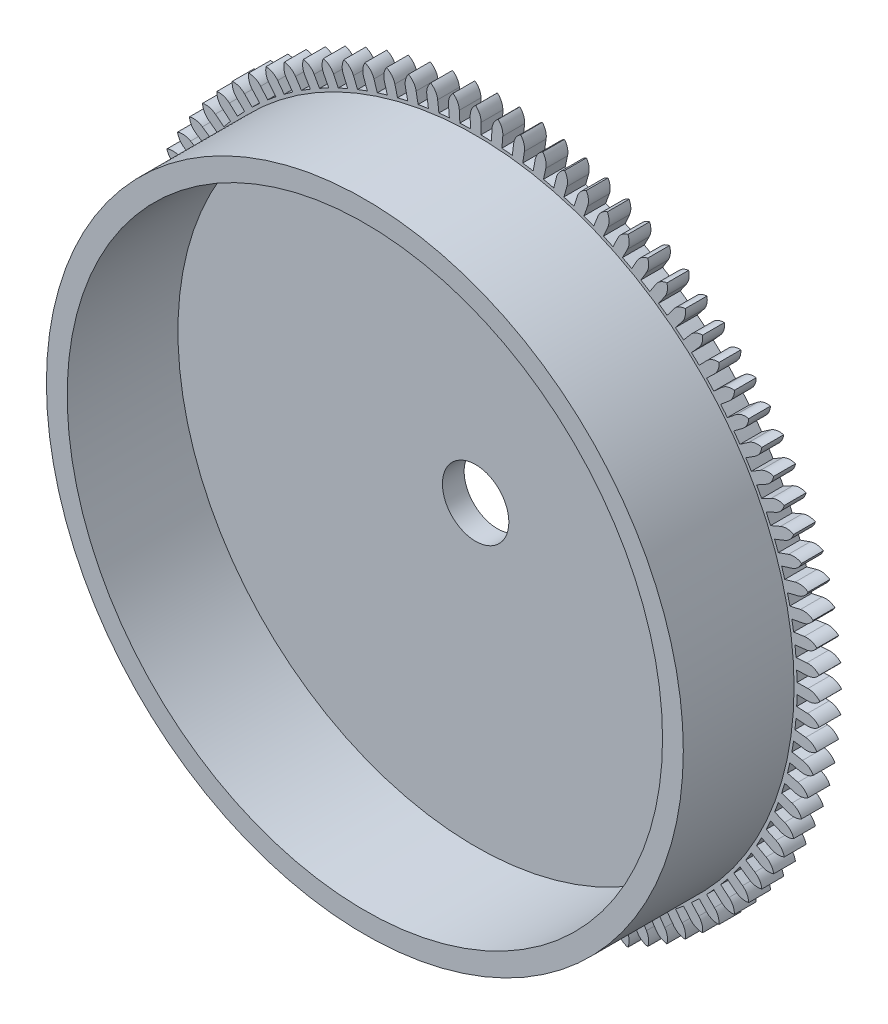
SolidWorks part; units mm, degrees
material "AISI 321 Annealed Stainless Steel (SS)"
ref_plane "Front Plane" through (0, 0, 0) normal (0, 0, 1) x (1, 0, 0)
ref_plane "Top Plane" through (0, 0, 0) normal (0, 1, 0) x (1, 0, 0)
ref_plane "Right Plane" through (0, 0, 0) normal (1, 0, 0) x (0, 0, -1)
sketch "Sketch1" plane through (0, 0, 0) normal (0, 0, 1) x (1, 0, 0)
  line L0 (0, 0) -> (0, 13.0514) construction
  line L1 (-0.1899, 11.6057) -> (-0.1963, 11.9984)
  line L2 (0.1899, 11.6057) -> (0.1963, 11.9984)
  line L3 (0.5695, 11.5933) -> (0.5888, 11.9855)
  line L4 (0.9486, 11.5685) -> (0.9807, 11.9599)
  line L5 (1.3266, 11.5312) -> (1.3714, 11.9214)
  line L6 (1.7031, 11.4817) -> (1.7608, 11.8701)
  line L7 (2.0779, 11.4198) -> (2.1482, 11.8062)
  line L8 (2.4504, 11.3457) -> (2.5333, 11.7295)
  line L9 (2.8203, 11.2594) -> (2.9158, 11.6404)
  line L10 (3.1872, 11.1611) -> (3.2951, 11.5387)
  line L11 (3.5507, 11.0509) -> (3.6708, 11.4248)
  line L12 (3.9104, 10.9288) -> (4.0427, 11.2985)
  line L13 (4.2659, 10.795) -> (4.4102, 11.1602)
  line L14 (4.6168, 10.6496) -> (4.773, 11.0099)
  line L15 (4.9628, 10.4929) -> (5.1307, 10.8479)
  line L16 (5.3034, 10.3249) -> (5.4828, 10.6742)
  line L17 (5.6384, 10.1458) -> (5.8292, 10.4891)
  line L18 (5.9673, 9.9559) -> (6.1692, 10.2927)
  line L19 (6.2899, 9.7553) -> (6.5027, 10.0854)
  line L20 (6.6057, 9.5443) -> (6.8292, 9.8672)
  line L21 (6.9145, 9.3231) -> (7.1484, 9.6385)
  line L22 (7.2158, 9.0918) -> (7.4599, 9.3994)
  line L23 (7.5094, 8.8509) -> (7.7635, 9.1503)
  line L24 (7.795, 8.6004) -> (8.0587, 8.8914)
  line L25 (8.0722, 8.3408) -> (8.3453, 8.623)
  line L26 (8.3408, 8.0722) -> (8.623, 8.3453)
  line L27 (8.6004, 7.795) -> (8.8914, 8.0587)
  line L28 (8.8509, 7.5094) -> (9.1503, 7.7635)
  line L29 (9.0918, 7.2158) -> (9.3994, 7.4599)
  line L30 (9.3231, 6.9145) -> (9.6385, 7.1484)
  line L31 (9.5443, 6.6057) -> (9.8672, 6.8292)
  line L32 (9.7553, 6.2899) -> (10.0854, 6.5027)
  line L33 (9.9559, 5.9673) -> (10.2927, 6.1692)
  line L34 (10.1458, 5.6384) -> (10.4891, 5.8292)
  line L35 (10.3249, 5.3034) -> (10.6742, 5.4828)
  line L36 (10.4929, 4.9628) -> (10.8479, 5.1307)
  line L37 (10.6496, 4.6168) -> (11.0099, 4.773)
  line L38 (10.795, 4.2659) -> (11.1602, 4.4102)
  line L39 (10.9288, 3.9104) -> (11.2985, 4.0427)
  line L40 (11.0509, 3.5507) -> (11.4248, 3.6708)
  line L41 (11.1611, 3.1872) -> (11.5387, 3.2951)
  line L42 (11.2594, 2.8203) -> (11.6404, 2.9158)
  line L43 (11.3457, 2.4504) -> (11.7295, 2.5333)
  line L44 (11.4198, 2.0779) -> (11.8062, 2.1482)
  line L45 (11.4817, 1.7031) -> (11.8701, 1.7608)
  line L46 (11.5312, 1.3266) -> (11.9214, 1.3714)
  line L47 (11.5685, 0.9486) -> (11.9599, 0.9807)
  line L48 (11.5933, 0.5695) -> (11.9855, 0.5888)
  line L49 (11.6057, 0.1899) -> (11.9984, 0.1963)
  line L50 (11.6057, -0.1899) -> (11.9984, -0.1963)
  line L51 (11.5933, -0.5695) -> (11.9855, -0.5888)
  line L52 (11.5685, -0.9486) -> (11.9599, -0.9807)
  line L53 (11.5312, -1.3266) -> (11.9214, -1.3714)
  line L54 (11.4817, -1.7031) -> (11.8701, -1.7608)
  line L55 (11.4198, -2.0779) -> (11.8062, -2.1482)
  line L56 (11.3457, -2.4504) -> (11.7295, -2.5333)
  line L57 (11.2594, -2.8203) -> (11.6404, -2.9158)
  line L58 (11.1611, -3.1872) -> (11.5387, -3.2951)
  line L59 (11.0509, -3.5507) -> (11.4248, -3.6708)
  line L60 (10.9288, -3.9104) -> (11.2985, -4.0427)
  line L61 (10.795, -4.2659) -> (11.1602, -4.4102)
  line L62 (10.6496, -4.6168) -> (11.0099, -4.773)
  line L63 (10.4929, -4.9628) -> (10.8479, -5.1307)
  line L64 (10.3249, -5.3034) -> (10.6742, -5.4828)
  line L65 (10.1458, -5.6384) -> (10.4891, -5.8292)
  line L66 (9.9559, -5.9673) -> (10.2927, -6.1692)
  line L67 (9.7553, -6.2899) -> (10.0854, -6.5027)
  line L68 (9.5443, -6.6057) -> (9.8672, -6.8292)
  line L69 (9.3231, -6.9145) -> (9.6385, -7.1484)
  line L70 (9.0918, -7.2158) -> (9.3994, -7.4599)
  line L71 (8.8509, -7.5094) -> (9.1503, -7.7635)
  line L72 (8.6004, -7.795) -> (8.8914, -8.0587)
  line L73 (8.3408, -8.0722) -> (8.623, -8.3453)
  line L74 (8.0722, -8.3408) -> (8.3453, -8.623)
  line L75 (7.795, -8.6004) -> (8.0587, -8.8914)
  line L76 (7.5094, -8.8509) -> (7.7635, -9.1503)
  line L77 (7.2158, -9.0918) -> (7.4599, -9.3994)
  line L78 (6.9145, -9.3231) -> (7.1484, -9.6385)
  line L79 (6.6057, -9.5443) -> (6.8292, -9.8672)
  line L80 (6.2899, -9.7553) -> (6.5027, -10.0854)
  line L81 (5.9673, -9.9559) -> (6.1692, -10.2927)
  line L82 (5.6384, -10.1458) -> (5.8292, -10.4891)
  line L83 (5.3034, -10.3249) -> (5.4828, -10.6742)
  line L84 (4.9628, -10.4929) -> (5.1307, -10.8479)
  line L85 (4.6168, -10.6496) -> (4.773, -11.0099)
  line L86 (4.2659, -10.795) -> (4.4102, -11.1602)
  line L87 (3.9104, -10.9288) -> (4.0427, -11.2985)
  line L88 (3.5507, -11.0509) -> (3.6708, -11.4248)
  line L89 (3.1872, -11.1611) -> (3.2951, -11.5387)
  line L90 (2.8203, -11.2594) -> (2.9158, -11.6404)
  line L91 (2.4504, -11.3457) -> (2.5333, -11.7295)
  line L92 (2.0779, -11.4198) -> (2.1482, -11.8062)
  line L93 (1.7031, -11.4817) -> (1.7608, -11.8701)
  line L94 (1.3266, -11.5312) -> (1.3714, -11.9214)
  line L95 (0.9486, -11.5685) -> (0.9807, -11.9599)
  line L96 (0.5695, -11.5933) -> (0.5888, -11.9855)
  line L97 (0.1899, -11.6057) -> (0.1963, -11.9984)
  line L98 (-0.1899, -11.6057) -> (-0.1963, -11.9984)
  line L99 (-0.5695, -11.5933) -> (-0.5888, -11.9855)
  line L100 (-0.9486, -11.5685) -> (-0.9807, -11.9599)
  line L101 (-1.3266, -11.5312) -> (-1.3714, -11.9214)
  line L102 (-1.7031, -11.4817) -> (-1.7608, -11.8701)
  line L103 (-2.0779, -11.4198) -> (-2.1482, -11.8062)
  line L104 (-2.4504, -11.3457) -> (-2.5333, -11.7295)
  line L105 (-2.8203, -11.2594) -> (-2.9158, -11.6404)
  line L106 (-3.1872, -11.1611) -> (-3.2951, -11.5387)
  line L107 (-3.5507, -11.0509) -> (-3.6708, -11.4248)
  line L108 (-3.9104, -10.9288) -> (-4.0427, -11.2985)
  line L109 (-4.2659, -10.795) -> (-4.4102, -11.1602)
  line L110 (-4.6168, -10.6496) -> (-4.773, -11.0099)
  line L111 (-4.9628, -10.4929) -> (-5.1307, -10.8479)
  line L112 (-5.3034, -10.3249) -> (-5.4828, -10.6742)
  line L113 (-5.6384, -10.1458) -> (-5.8292, -10.4891)
  line L114 (-5.9673, -9.9559) -> (-6.1692, -10.2927)
  line L115 (-6.2899, -9.7553) -> (-6.5027, -10.0854)
  line L116 (-6.6057, -9.5443) -> (-6.8292, -9.8672)
  line L117 (-6.9145, -9.3231) -> (-7.1484, -9.6385)
  line L118 (-7.2158, -9.0918) -> (-7.4599, -9.3994)
  line L119 (-7.5094, -8.8509) -> (-7.7635, -9.1503)
  line L120 (-7.795, -8.6004) -> (-8.0587, -8.8914)
  line L121 (-8.0722, -8.3408) -> (-8.3453, -8.623)
  line L122 (-8.3408, -8.0722) -> (-8.623, -8.3453)
  line L123 (-8.6004, -7.795) -> (-8.8914, -8.0587)
  line L124 (-8.8509, -7.5094) -> (-9.1503, -7.7635)
  line L125 (-9.0918, -7.2158) -> (-9.3994, -7.4599)
  line L126 (-9.3231, -6.9145) -> (-9.6385, -7.1484)
  line L127 (-9.5443, -6.6057) -> (-9.8672, -6.8292)
  line L128 (-9.7553, -6.2899) -> (-10.0854, -6.5027)
  line L129 (-9.9559, -5.9673) -> (-10.2927, -6.1692)
  line L130 (-10.1458, -5.6384) -> (-10.4891, -5.8292)
  line L131 (-10.3249, -5.3034) -> (-10.6742, -5.4828)
  line L132 (-10.4929, -4.9628) -> (-10.8479, -5.1307)
  line L133 (-10.6496, -4.6168) -> (-11.0099, -4.773)
  line L134 (-10.795, -4.2659) -> (-11.1602, -4.4102)
  line L135 (-10.9288, -3.9104) -> (-11.2985, -4.0427)
  line L136 (-11.0509, -3.5507) -> (-11.4248, -3.6708)
  line L137 (-11.1611, -3.1872) -> (-11.5387, -3.2951)
  line L138 (-11.2594, -2.8203) -> (-11.6404, -2.9158)
  line L139 (-11.3457, -2.4504) -> (-11.7295, -2.5333)
  line L140 (-11.4198, -2.0779) -> (-11.8062, -2.1482)
  line L141 (-11.4817, -1.7031) -> (-11.8701, -1.7608)
  line L142 (-11.5312, -1.3266) -> (-11.9214, -1.3714)
  line L143 (-11.5685, -0.9486) -> (-11.9599, -0.9807)
  line L144 (-11.5933, -0.5695) -> (-11.9855, -0.5888)
  line L145 (-11.6057, -0.1899) -> (-11.9984, -0.1963)
  line L146 (-11.6057, 0.1899) -> (-11.9984, 0.1963)
  line L147 (-11.5933, 0.5695) -> (-11.9855, 0.5888)
  line L148 (-11.5685, 0.9486) -> (-11.9599, 0.9807)
  line L149 (-11.5312, 1.3266) -> (-11.9214, 1.3714)
  line L150 (-11.4817, 1.7031) -> (-11.8701, 1.7608)
  line L151 (-11.4198, 2.0779) -> (-11.8062, 2.1482)
  line L152 (-11.3457, 2.4504) -> (-11.7295, 2.5333)
  line L153 (-11.2594, 2.8203) -> (-11.6404, 2.9158)
  line L154 (-11.1611, 3.1872) -> (-11.5387, 3.2951)
  line L155 (-11.0509, 3.5507) -> (-11.4248, 3.6708)
  line L156 (-10.9288, 3.9104) -> (-11.2985, 4.0427)
  line L157 (-10.795, 4.2659) -> (-11.1602, 4.4102)
  line L158 (-10.6496, 4.6168) -> (-11.0099, 4.773)
  line L159 (-10.4929, 4.9628) -> (-10.8479, 5.1307)
  line L160 (-10.3249, 5.3034) -> (-10.6742, 5.4828)
  line L161 (-10.1458, 5.6384) -> (-10.4891, 5.8292)
  line L162 (-9.9559, 5.9673) -> (-10.2927, 6.1692)
  line L163 (-9.7553, 6.2899) -> (-10.0854, 6.5027)
  line L164 (-9.5443, 6.6057) -> (-9.8672, 6.8292)
  line L165 (-9.3231, 6.9145) -> (-9.6385, 7.1484)
  line L166 (-9.0918, 7.2158) -> (-9.3994, 7.4599)
  line L167 (-8.8509, 7.5094) -> (-9.1503, 7.7635)
  line L168 (-8.6004, 7.795) -> (-8.8914, 8.0587)
  line L169 (-8.3408, 8.0722) -> (-8.623, 8.3453)
  line L170 (-8.0722, 8.3408) -> (-8.3453, 8.623)
  line L171 (-7.795, 8.6004) -> (-8.0587, 8.8914)
  line L172 (-7.5094, 8.8509) -> (-7.7635, 9.1503)
  line L173 (-7.2158, 9.0918) -> (-7.4599, 9.3994)
  line L174 (-6.9145, 9.3231) -> (-7.1484, 9.6385)
  line L175 (-6.6057, 9.5443) -> (-6.8292, 9.8672)
  line L176 (-6.2899, 9.7553) -> (-6.5027, 10.0854)
  line L177 (-5.9673, 9.9559) -> (-6.1692, 10.2927)
  line L178 (-5.6384, 10.1458) -> (-5.8292, 10.4891)
  line L179 (-5.3034, 10.3249) -> (-5.4828, 10.6742)
  line L180 (-4.9628, 10.4929) -> (-5.1307, 10.8479)
  line L181 (-4.6168, 10.6496) -> (-4.773, 11.0099)
  line L182 (-4.2659, 10.795) -> (-4.4102, 11.1602)
  line L183 (-3.9104, 10.9288) -> (-4.0427, 11.2985)
  line L184 (-3.5507, 11.0509) -> (-3.6708, 11.4248)
  line L185 (-3.1872, 11.1611) -> (-3.2951, 11.5387)
  line L186 (-2.8203, 11.2594) -> (-2.9158, 11.6404)
  line L187 (-2.4504, 11.3457) -> (-2.5333, 11.7295)
  line L188 (-2.0779, 11.4198) -> (-2.1482, 11.8062)
  line L189 (-1.7031, 11.4817) -> (-1.7608, 11.8701)
  line L190 (-1.3266, 11.5312) -> (-1.3714, 11.9214)
  line L191 (-0.9486, 11.5685) -> (-0.9807, 11.9599)
  line L192 (-0.5695, 11.5933) -> (-0.5888, 11.9855)
  arc A0 (0.5695, 11.5933) -> (0.1899, 11.6057) centre (0, 0) ccw
  arc A1 (-0.1899, 11.6057) -> (-0.5695, 11.5933) centre (0, 0) ccw
  arc A2 (1.3266, 11.5312) -> (0.9486, 11.5685) centre (0, 0) ccw
  arc A3 (-0.1963, 11.9984) -> (0, 12.4305) centre (0.3574, 12.0075) cw
  arc A4 (0.1963, 11.9984) -> (0, 12.4305) centre (-0.3574, 12.0075) ccw
  arc A5 (0.5888, 11.9855) -> (0.813, 12.4039) centre (1.1419, 11.9584) cw
  arc A6 (0.9807, 11.9599) -> (0.813, 12.4039) centre (0.4287, 12.0051) ccw
  arc A7 (1.3714, 11.9214) -> (1.6225, 12.3242) centre (1.9216, 11.8581) cw
  arc A8 (1.7608, 11.8701) -> (1.6225, 12.3242) centre (1.213, 11.9514) ccw
  arc A9 (2.1482, 11.8062) -> (2.4251, 12.1917) centre (2.693, 11.707) cw
  arc A10 (2.5333, 11.7295) -> (2.4251, 12.1917) centre (1.992, 11.8465) ccw
  arc A11 (2.9158, 11.6404) -> (3.2173, 12.0069) centre (3.453, 11.5058) cw
  arc A12 (3.2951, 11.5387) -> (3.2173, 12.0069) centre (2.7626, 11.6908) ccw
  arc A13 (3.6708, 11.4248) -> (3.9957, 11.7708) centre (4.1981, 11.2553) cw
  arc A14 (4.0427, 11.2985) -> (3.9957, 11.7708) centre (3.5213, 11.4851) ccw
  arc A15 (4.4102, 11.1602) -> (4.7569, 11.4843) centre (4.9252, 10.9567) cw
  arc A16 (4.773, 11.0099) -> (4.7569, 11.4843) centre (4.2649, 11.2302) ccw
  arc A17 (5.1307, 10.8479) -> (5.4979, 11.1486) centre (5.6313, 10.6111) cw
  arc A18 (5.4828, 10.6742) -> (5.4979, 11.1486) centre (4.9902, 10.9272) ccw
  arc A19 (5.8292, 10.4891) -> (6.2153, 10.7651) centre (6.3132, 10.2201) cw
  arc A20 (6.1692, 10.2927) -> (6.2153, 10.7651) centre (5.6942, 10.5774) ccw
  arc A21 (6.5027, 10.0854) -> (6.906, 10.3356) centre (6.9681, 9.7853) cw
  arc A22 (6.8292, 9.8672) -> (6.906, 10.3356) centre (6.3738, 10.1824) ccw
  arc A23 (7.1484, 9.6385) -> (7.5672, 9.8618) centre (7.5932, 9.3086) cw
  arc A24 (7.4599, 9.3994) -> (7.5672, 9.8618) centre (7.0262, 9.7437) ccw
  arc A25 (7.7635, 9.1503) -> (8.196, 9.3457) centre (8.1857, 8.7921) cw
  arc A26 (8.0587, 8.8914) -> (8.196, 9.3457) centre (7.6484, 9.2633) ccw
  arc A27 (8.3453, 8.623) -> (8.7897, 8.7897) centre (8.7433, 8.2379) cw
  arc A28 (8.623, 8.3453) -> (8.7897, 8.7897) centre (8.2379, 8.7433) ccw
  arc A29 (8.8914, 8.0587) -> (9.3457, 8.196) centre (9.2633, 7.6484) cw
  arc A30 (9.1503, 7.7635) -> (9.3457, 8.196) centre (8.7921, 8.1857) ccw
  arc A31 (9.3994, 7.4599) -> (9.8618, 7.5672) centre (9.7437, 7.0262) cw
  arc A32 (9.6385, 7.1484) -> (9.8618, 7.5672) centre (9.3086, 7.5932) ccw
  arc A33 (9.8672, 6.8292) -> (10.3356, 6.906) centre (10.1824, 6.3738) cw
  arc A34 (10.0854, 6.5027) -> (10.3356, 6.906) centre (9.7853, 6.9681) ccw
  arc A35 (10.2927, 6.1692) -> (10.7651, 6.2153) centre (10.5774, 5.6942) cw
  arc A36 (10.4891, 5.8292) -> (10.7651, 6.2153) centre (10.2201, 6.3132) ccw
  arc A37 (10.6742, 5.4828) -> (11.1486, 5.4979) centre (10.9272, 4.9902) cw
  arc A38 (10.8479, 5.1307) -> (11.1486, 5.4979) centre (10.6111, 5.6313) ccw
  arc A39 (11.0099, 4.773) -> (11.4843, 4.7569) centre (11.2302, 4.2649) cw
  arc A40 (11.1602, 4.4102) -> (11.4843, 4.7569) centre (10.9567, 4.9252) ccw
  arc A41 (11.2985, 4.0427) -> (11.7708, 3.9957) centre (11.4851, 3.5213) cw
  arc A42 (11.4248, 3.6708) -> (11.7708, 3.9957) centre (11.2553, 4.1981) ccw
  arc A43 (11.5387, 3.2951) -> (12.0069, 3.2173) centre (11.6908, 2.7626) cw
  arc A44 (11.6404, 2.9158) -> (12.0069, 3.2173) centre (11.5058, 3.453) ccw
  arc A45 (11.7295, 2.5333) -> (12.1917, 2.4251) centre (11.8465, 1.992) cw
  arc A46 (11.8062, 2.1482) -> (12.1917, 2.4251) centre (11.707, 2.693) ccw
  arc A47 (11.8701, 1.7608) -> (12.3242, 1.6225) centre (11.9514, 1.213) cw
  arc A48 (11.9214, 1.3714) -> (12.3242, 1.6225) centre (11.8581, 1.9216) ccw
  arc A49 (11.9599, 0.9807) -> (12.4039, 0.813) centre (12.0051, 0.4287) cw
  arc A50 (11.9855, 0.5888) -> (12.4039, 0.813) centre (11.9584, 1.1419) ccw
  arc A51 (11.9984, 0.1963) -> (12.4305, 0) centre (12.0075, -0.3574) cw
  arc A52 (11.9984, -0.1963) -> (12.4305, 0) centre (12.0075, 0.3574) ccw
  arc A53 (11.9855, -0.5888) -> (12.4039, -0.813) centre (11.9584, -1.1419) cw
  arc A54 (11.9599, -0.9807) -> (12.4039, -0.813) centre (12.0051, -0.4287) ccw
  arc A55 (11.9214, -1.3714) -> (12.3242, -1.6225) centre (11.8581, -1.9216) cw
  arc A56 (11.8701, -1.7608) -> (12.3242, -1.6225) centre (11.9514, -1.213) ccw
  arc A57 (11.8062, -2.1482) -> (12.1917, -2.4251) centre (11.707, -2.693) cw
  arc A58 (11.7295, -2.5333) -> (12.1917, -2.4251) centre (11.8465, -1.992) ccw
  arc A59 (11.6404, -2.9158) -> (12.0069, -3.2173) centre (11.5058, -3.453) cw
  arc A60 (11.5387, -3.2951) -> (12.0069, -3.2173) centre (11.6908, -2.7626) ccw
  arc A61 (11.4248, -3.6708) -> (11.7708, -3.9957) centre (11.2553, -4.1981) cw
  arc A62 (11.2985, -4.0427) -> (11.7708, -3.9957) centre (11.4851, -3.5213) ccw
  arc A63 (11.1602, -4.4102) -> (11.4843, -4.7569) centre (10.9567, -4.9252) cw
  arc A64 (11.0099, -4.773) -> (11.4843, -4.7569) centre (11.2302, -4.2649) ccw
  arc A65 (10.8479, -5.1307) -> (11.1486, -5.4979) centre (10.6111, -5.6313) cw
  arc A66 (10.6742, -5.4828) -> (11.1486, -5.4979) centre (10.9272, -4.9902) ccw
  arc A67 (10.4891, -5.8292) -> (10.7651, -6.2153) centre (10.2201, -6.3132) cw
  arc A68 (10.2927, -6.1692) -> (10.7651, -6.2153) centre (10.5774, -5.6942) ccw
  arc A69 (10.0854, -6.5027) -> (10.3356, -6.906) centre (9.7853, -6.9681) cw
  arc A70 (9.8672, -6.8292) -> (10.3356, -6.906) centre (10.1824, -6.3738) ccw
  arc A71 (9.6385, -7.1484) -> (9.8618, -7.5672) centre (9.3086, -7.5932) cw
  arc A72 (9.3994, -7.4599) -> (9.8618, -7.5672) centre (9.7437, -7.0262) ccw
  arc A73 (9.1503, -7.7635) -> (9.3457, -8.196) centre (8.7921, -8.1857) cw
  arc A74 (8.8914, -8.0587) -> (9.3457, -8.196) centre (9.2633, -7.6484) ccw
  arc A75 (8.623, -8.3453) -> (8.7897, -8.7897) centre (8.2379, -8.7433) cw
  arc A76 (8.3453, -8.623) -> (8.7897, -8.7897) centre (8.7433, -8.2379) ccw
  arc A77 (8.0587, -8.8914) -> (8.196, -9.3457) centre (7.6484, -9.2633) cw
  arc A78 (7.7635, -9.1503) -> (8.196, -9.3457) centre (8.1857, -8.7921) ccw
  arc A79 (7.4599, -9.3994) -> (7.5672, -9.8618) centre (7.0262, -9.7437) cw
  arc A80 (7.1484, -9.6385) -> (7.5672, -9.8618) centre (7.5932, -9.3086) ccw
  arc A81 (6.8292, -9.8672) -> (6.906, -10.3356) centre (6.3738, -10.1824) cw
  arc A82 (6.5027, -10.0854) -> (6.906, -10.3356) centre (6.9681, -9.7853) ccw
  arc A83 (6.1692, -10.2927) -> (6.2153, -10.7651) centre (5.6942, -10.5774) cw
  arc A84 (5.8292, -10.4891) -> (6.2153, -10.7651) centre (6.3132, -10.2201) ccw
  arc A85 (5.4828, -10.6742) -> (5.4979, -11.1486) centre (4.9902, -10.9272) cw
  arc A86 (5.1307, -10.8479) -> (5.4979, -11.1486) centre (5.6313, -10.6111) ccw
  arc A87 (4.773, -11.0099) -> (4.7569, -11.4843) centre (4.2649, -11.2302) cw
  arc A88 (4.4102, -11.1602) -> (4.7569, -11.4843) centre (4.9252, -10.9567) ccw
  arc A89 (4.0427, -11.2985) -> (3.9957, -11.7708) centre (3.5213, -11.4851) cw
  arc A90 (3.6708, -11.4248) -> (3.9957, -11.7708) centre (4.1981, -11.2553) ccw
  arc A91 (3.2951, -11.5387) -> (3.2173, -12.0069) centre (2.7626, -11.6908) cw
  arc A92 (2.9158, -11.6404) -> (3.2173, -12.0069) centre (3.453, -11.5058) ccw
  arc A93 (2.5333, -11.7295) -> (2.4251, -12.1917) centre (1.992, -11.8465) cw
  arc A94 (2.1482, -11.8062) -> (2.4251, -12.1917) centre (2.693, -11.707) ccw
  arc A95 (1.7608, -11.8701) -> (1.6225, -12.3242) centre (1.213, -11.9514) cw
  arc A96 (1.3714, -11.9214) -> (1.6225, -12.3242) centre (1.9216, -11.8581) ccw
  arc A97 (0.9807, -11.9599) -> (0.813, -12.4039) centre (0.4287, -12.0051) cw
  arc A98 (0.5888, -11.9855) -> (0.813, -12.4039) centre (1.1419, -11.9584) ccw
  arc A99 (0.1963, -11.9984) -> (0, -12.4305) centre (-0.3574, -12.0075) cw
  arc A100 (-0.1963, -11.9984) -> (0, -12.4305) centre (0.3574, -12.0075) ccw
  arc A101 (-0.5888, -11.9855) -> (-0.813, -12.4039) centre (-1.1419, -11.9584) cw
  arc A102 (-0.9807, -11.9599) -> (-0.813, -12.4039) centre (-0.4287, -12.0051) ccw
  arc A103 (-1.3714, -11.9214) -> (-1.6225, -12.3242) centre (-1.9216, -11.8581) cw
  arc A104 (-1.7608, -11.8701) -> (-1.6225, -12.3242) centre (-1.213, -11.9514) ccw
  arc A105 (-2.1482, -11.8062) -> (-2.4251, -12.1917) centre (-2.693, -11.707) cw
  arc A106 (-2.5333, -11.7295) -> (-2.4251, -12.1917) centre (-1.992, -11.8465) ccw
  arc A107 (-2.9158, -11.6404) -> (-3.2173, -12.0069) centre (-3.453, -11.5058) cw
  arc A108 (-3.2951, -11.5387) -> (-3.2173, -12.0069) centre (-2.7626, -11.6908) ccw
  arc A109 (-3.6708, -11.4248) -> (-3.9957, -11.7708) centre (-4.1981, -11.2553) cw
  arc A110 (-4.0427, -11.2985) -> (-3.9957, -11.7708) centre (-3.5213, -11.4851) ccw
  arc A111 (-4.4102, -11.1602) -> (-4.7569, -11.4843) centre (-4.9252, -10.9567) cw
  arc A112 (-4.773, -11.0099) -> (-4.7569, -11.4843) centre (-4.2649, -11.2302) ccw
  arc A113 (-5.1307, -10.8479) -> (-5.4979, -11.1486) centre (-5.6313, -10.6111) cw
  arc A114 (-5.4828, -10.6742) -> (-5.4979, -11.1486) centre (-4.9902, -10.9272) ccw
  arc A115 (-5.8292, -10.4891) -> (-6.2153, -10.7651) centre (-6.3132, -10.2201) cw
  arc A116 (-6.1692, -10.2927) -> (-6.2153, -10.7651) centre (-5.6942, -10.5774) ccw
  arc A117 (-6.5027, -10.0854) -> (-6.906, -10.3356) centre (-6.9681, -9.7853) cw
  arc A118 (-6.8292, -9.8672) -> (-6.906, -10.3356) centre (-6.3738, -10.1824) ccw
  arc A119 (-7.1484, -9.6385) -> (-7.5672, -9.8618) centre (-7.5932, -9.3086) cw
  arc A120 (-7.4599, -9.3994) -> (-7.5672, -9.8618) centre (-7.0262, -9.7437) ccw
  arc A121 (-7.7635, -9.1503) -> (-8.196, -9.3457) centre (-8.1857, -8.7921) cw
  arc A122 (-8.0587, -8.8914) -> (-8.196, -9.3457) centre (-7.6484, -9.2633) ccw
  arc A123 (-8.3453, -8.623) -> (-8.7897, -8.7897) centre (-8.7433, -8.2379) cw
  arc A124 (-8.623, -8.3453) -> (-8.7897, -8.7897) centre (-8.2379, -8.7433) ccw
  arc A125 (-8.8914, -8.0587) -> (-9.3457, -8.196) centre (-9.2633, -7.6484) cw
  arc A126 (-9.1503, -7.7635) -> (-9.3457, -8.196) centre (-8.7921, -8.1857) ccw
  arc A127 (-9.3994, -7.4599) -> (-9.8618, -7.5672) centre (-9.7437, -7.0262) cw
  arc A128 (-9.6385, -7.1484) -> (-9.8618, -7.5672) centre (-9.3086, -7.5932) ccw
  arc A129 (-9.8672, -6.8292) -> (-10.3356, -6.906) centre (-10.1824, -6.3738) cw
  arc A130 (-10.0854, -6.5027) -> (-10.3356, -6.906) centre (-9.7853, -6.9681) ccw
  arc A131 (-10.2927, -6.1692) -> (-10.7651, -6.2153) centre (-10.5774, -5.6942) cw
  arc A132 (-10.4891, -5.8292) -> (-10.7651, -6.2153) centre (-10.2201, -6.3132) ccw
  arc A133 (-10.6742, -5.4828) -> (-11.1486, -5.4979) centre (-10.9272, -4.9902) cw
  arc A134 (-10.8479, -5.1307) -> (-11.1486, -5.4979) centre (-10.6111, -5.6313) ccw
  arc A135 (-11.0099, -4.773) -> (-11.4843, -4.7569) centre (-11.2302, -4.2649) cw
  arc A136 (-11.1602, -4.4102) -> (-11.4843, -4.7569) centre (-10.9567, -4.9252) ccw
  arc A137 (-11.2985, -4.0427) -> (-11.7708, -3.9957) centre (-11.4851, -3.5213) cw
  arc A138 (-11.4248, -3.6708) -> (-11.7708, -3.9957) centre (-11.2553, -4.1981) ccw
  arc A139 (-11.5387, -3.2951) -> (-12.0069, -3.2173) centre (-11.6908, -2.7626) cw
  arc A140 (-11.6404, -2.9158) -> (-12.0069, -3.2173) centre (-11.5058, -3.453) ccw
  arc A141 (-11.7295, -2.5333) -> (-12.1917, -2.4251) centre (-11.8465, -1.992) cw
  arc A142 (-11.8062, -2.1482) -> (-12.1917, -2.4251) centre (-11.707, -2.693) ccw
  arc A143 (-11.8701, -1.7608) -> (-12.3242, -1.6225) centre (-11.9514, -1.213) cw
  arc A144 (-11.9214, -1.3714) -> (-12.3242, -1.6225) centre (-11.8581, -1.9216) ccw
  arc A145 (-11.9599, -0.9807) -> (-12.4039, -0.813) centre (-12.0051, -0.4287) cw
  arc A146 (-11.9855, -0.5888) -> (-12.4039, -0.813) centre (-11.9584, -1.1419) ccw
  arc A147 (-11.9984, -0.1963) -> (-12.4305, 0) centre (-12.0075, 0.3574) cw
  arc A148 (-11.9984, 0.1963) -> (-12.4305, 0) centre (-12.0075, -0.3574) ccw
  arc A149 (-11.9855, 0.5888) -> (-12.4039, 0.813) centre (-11.9584, 1.1419) cw
  arc A150 (-11.9599, 0.9807) -> (-12.4039, 0.813) centre (-12.0051, 0.4287) ccw
  arc A151 (-11.9214, 1.3714) -> (-12.3242, 1.6225) centre (-11.8581, 1.9216) cw
  arc A152 (-11.8701, 1.7608) -> (-12.3242, 1.6225) centre (-11.9514, 1.213) ccw
  arc A153 (-11.8062, 2.1482) -> (-12.1917, 2.4251) centre (-11.707, 2.693) cw
  arc A154 (-11.7295, 2.5333) -> (-12.1917, 2.4251) centre (-11.8465, 1.992) ccw
  arc A155 (-11.6404, 2.9158) -> (-12.0069, 3.2173) centre (-11.5058, 3.453) cw
  arc A156 (-11.5387, 3.2951) -> (-12.0069, 3.2173) centre (-11.6908, 2.7626) ccw
  arc A157 (-11.4248, 3.6708) -> (-11.7708, 3.9957) centre (-11.2553, 4.1981) cw
  arc A158 (-11.2985, 4.0427) -> (-11.7708, 3.9957) centre (-11.4851, 3.5213) ccw
  arc A159 (-11.1602, 4.4102) -> (-11.4843, 4.7569) centre (-10.9567, 4.9252) cw
  arc A160 (-11.0099, 4.773) -> (-11.4843, 4.7569) centre (-11.2302, 4.2649) ccw
  arc A161 (-10.8479, 5.1307) -> (-11.1486, 5.4979) centre (-10.6111, 5.6313) cw
  arc A162 (-10.6742, 5.4828) -> (-11.1486, 5.4979) centre (-10.9272, 4.9902) ccw
  arc A163 (-10.4891, 5.8292) -> (-10.7651, 6.2153) centre (-10.2201, 6.3132) cw
  arc A164 (-10.2927, 6.1692) -> (-10.7651, 6.2153) centre (-10.5774, 5.6942) ccw
  arc A165 (-10.0854, 6.5027) -> (-10.3356, 6.906) centre (-9.7853, 6.9681) cw
  arc A166 (-9.8672, 6.8292) -> (-10.3356, 6.906) centre (-10.1824, 6.3738) ccw
  arc A167 (-9.6385, 7.1484) -> (-9.8618, 7.5672) centre (-9.3086, 7.5932) cw
  arc A168 (-9.3994, 7.4599) -> (-9.8618, 7.5672) centre (-9.7437, 7.0262) ccw
  arc A169 (-9.1503, 7.7635) -> (-9.3457, 8.196) centre (-8.7921, 8.1857) cw
  arc A170 (-8.8914, 8.0587) -> (-9.3457, 8.196) centre (-9.2633, 7.6484) ccw
  arc A171 (-8.623, 8.3453) -> (-8.7897, 8.7897) centre (-8.2379, 8.7433) cw
  arc A172 (-8.3453, 8.623) -> (-8.7897, 8.7897) centre (-8.7433, 8.2379) ccw
  arc A173 (-8.0587, 8.8914) -> (-8.196, 9.3457) centre (-7.6484, 9.2633) cw
  arc A174 (-7.7635, 9.1503) -> (-8.196, 9.3457) centre (-8.1857, 8.7921) ccw
  arc A175 (-7.4599, 9.3994) -> (-7.5672, 9.8618) centre (-7.0262, 9.7437) cw
  arc A176 (-7.1484, 9.6385) -> (-7.5672, 9.8618) centre (-7.5932, 9.3086) ccw
  arc A177 (-6.8292, 9.8672) -> (-6.906, 10.3356) centre (-6.3738, 10.1824) cw
  arc A178 (-6.5027, 10.0854) -> (-6.906, 10.3356) centre (-6.9681, 9.7853) ccw
  arc A179 (-6.1692, 10.2927) -> (-6.2152, 10.7651) centre (-5.6942, 10.5774) cw
  arc A180 (-5.8292, 10.4891) -> (-6.2152, 10.7651) centre (-6.3132, 10.2201) ccw
  arc A181 (-5.4828, 10.6742) -> (-5.4979, 11.1486) centre (-4.9902, 10.9272) cw
  arc A182 (-5.1307, 10.8479) -> (-5.4979, 11.1486) centre (-5.6313, 10.6111) ccw
  arc A183 (-4.773, 11.0099) -> (-4.7569, 11.4843) centre (-4.2649, 11.2302) cw
  arc A184 (-4.4102, 11.1602) -> (-4.7569, 11.4843) centre (-4.9252, 10.9567) ccw
  arc A185 (-4.0427, 11.2985) -> (-3.9957, 11.7708) centre (-3.5213, 11.4851) cw
  arc A186 (-3.6708, 11.4248) -> (-3.9957, 11.7708) centre (-4.1981, 11.2553) ccw
  arc A187 (-3.2951, 11.5387) -> (-3.2173, 12.0069) centre (-2.7626, 11.6908) cw
  arc A188 (-2.9158, 11.6404) -> (-3.2173, 12.0069) centre (-3.453, 11.5058) ccw
  arc A189 (-2.5333, 11.7295) -> (-2.4251, 12.1917) centre (-1.992, 11.8465) cw
  arc A190 (-2.1482, 11.8062) -> (-2.4251, 12.1917) centre (-2.693, 11.707) ccw
  arc A191 (-1.7608, 11.8701) -> (-1.6225, 12.3242) centre (-1.213, 11.9514) cw
  arc A192 (-1.3714, 11.9214) -> (-1.6225, 12.3242) centre (-1.9216, 11.8581) ccw
  arc A193 (-0.9807, 11.9599) -> (-0.813, 12.4039) centre (-0.4287, 12.0051) cw
  arc A194 (-0.5888, 11.9855) -> (-0.813, 12.4039) centre (-1.1419, 11.9584) ccw
  arc A195 (-0.9486, 11.5685) -> (-1.3266, 11.5312) centre (0, 0) ccw
  arc A196 (-1.7031, 11.4817) -> (-2.0779, 11.4198) centre (0, 0) ccw
  arc A197 (-2.4504, 11.3457) -> (-2.8203, 11.2594) centre (0, 0) ccw
  arc A198 (-3.1872, 11.1611) -> (-3.5507, 11.0509) centre (0, 0) ccw
  arc A199 (-3.9104, 10.9288) -> (-4.2659, 10.795) centre (0, 0) ccw
  arc A200 (-4.6168, 10.6496) -> (-4.9628, 10.4929) centre (0, 0) ccw
  arc A201 (-5.3034, 10.3249) -> (-5.6384, 10.1458) centre (0, 0) ccw
  arc A202 (-5.9673, 9.9559) -> (-6.2899, 9.7553) centre (0, 0) ccw
  arc A203 (-6.6057, 9.5443) -> (-6.9145, 9.3231) centre (0, 0) ccw
  arc A204 (-7.2158, 9.0918) -> (-7.5094, 8.8509) centre (0, 0) ccw
  arc A205 (-7.795, 8.6004) -> (-8.0722, 8.3408) centre (0, 0) ccw
  arc A206 (-8.3408, 8.0722) -> (-8.6004, 7.795) centre (0, 0) ccw
  arc A207 (-8.8509, 7.5094) -> (-9.0918, 7.2158) centre (0, 0) ccw
  arc A208 (-9.3231, 6.9145) -> (-9.5443, 6.6057) centre (0, 0) ccw
  arc A209 (-9.7553, 6.2899) -> (-9.9559, 5.9673) centre (0, 0) ccw
  arc A210 (-10.1458, 5.6384) -> (-10.3249, 5.3034) centre (0, 0) ccw
  arc A211 (-10.4929, 4.9628) -> (-10.6496, 4.6168) centre (0, 0) ccw
  arc A212 (-10.795, 4.2659) -> (-10.9288, 3.9104) centre (0, 0) ccw
  arc A213 (-11.0509, 3.5507) -> (-11.1611, 3.1872) centre (0, 0) ccw
  arc A214 (-11.2594, 2.8203) -> (-11.3457, 2.4504) centre (0, 0) ccw
  arc A215 (-11.4198, 2.0779) -> (-11.4817, 1.7031) centre (0, 0) ccw
  arc A216 (-11.5312, 1.3266) -> (-11.5685, 0.9486) centre (0, 0) ccw
  arc A217 (-11.5933, 0.5695) -> (-11.6057, 0.1899) centre (0, 0) ccw
  arc A218 (-11.6057, -0.1899) -> (-11.5933, -0.5695) centre (0, 0) ccw
  arc A219 (-11.5685, -0.9486) -> (-11.5312, -1.3266) centre (0, 0) ccw
  arc A220 (-11.4817, -1.7031) -> (-11.4198, -2.0779) centre (0, 0) ccw
  arc A221 (-11.3457, -2.4504) -> (-11.2594, -2.8203) centre (0, 0) ccw
  arc A222 (-11.1611, -3.1872) -> (-11.0509, -3.5507) centre (0, 0) ccw
  arc A223 (-10.9288, -3.9104) -> (-10.795, -4.2659) centre (0, 0) ccw
  arc A224 (-10.6496, -4.6168) -> (-10.4929, -4.9628) centre (0, 0) ccw
  arc A225 (-10.3249, -5.3034) -> (-10.1458, -5.6384) centre (0, 0) ccw
  arc A226 (-9.9559, -5.9673) -> (-9.7553, -6.2899) centre (0, 0) ccw
  arc A227 (-9.5443, -6.6057) -> (-9.3231, -6.9145) centre (0, 0) ccw
  arc A228 (-9.0918, -7.2158) -> (-8.8509, -7.5094) centre (0, 0) ccw
  arc A229 (-8.6004, -7.795) -> (-8.3408, -8.0722) centre (0, 0) ccw
  arc A230 (-8.0722, -8.3408) -> (-7.795, -8.6004) centre (0, 0) ccw
  arc A231 (-7.5094, -8.8509) -> (-7.2158, -9.0918) centre (0, 0) ccw
  arc A232 (-6.9145, -9.3231) -> (-6.6057, -9.5443) centre (0, 0) ccw
  arc A233 (-6.2899, -9.7553) -> (-5.9673, -9.9559) centre (0, 0) ccw
  arc A234 (-5.6384, -10.1458) -> (-5.3034, -10.3249) centre (0, 0) ccw
  arc A235 (-4.9628, -10.4929) -> (-4.6168, -10.6496) centre (0, 0) ccw
  arc A236 (-4.2659, -10.795) -> (-3.9104, -10.9288) centre (0, 0) ccw
  arc A237 (-3.5507, -11.0509) -> (-3.1872, -11.1611) centre (0, 0) ccw
  arc A238 (-2.8203, -11.2594) -> (-2.4504, -11.3457) centre (0, 0) ccw
  arc A239 (-2.0779, -11.4198) -> (-1.7031, -11.4817) centre (0, 0) ccw
  arc A240 (-1.3266, -11.5312) -> (-0.9486, -11.5685) centre (0, 0) ccw
  arc A241 (-0.5695, -11.5933) -> (-0.1899, -11.6057) centre (0, 0) ccw
  arc A242 (0.1899, -11.6057) -> (0.5695, -11.5933) centre (0, 0) ccw
  arc A243 (0.9486, -11.5685) -> (1.3266, -11.5312) centre (0, 0) ccw
  arc A244 (1.7031, -11.4817) -> (2.0779, -11.4198) centre (0, 0) ccw
  arc A245 (2.4504, -11.3457) -> (2.8203, -11.2594) centre (0, 0) ccw
  arc A246 (3.1872, -11.1611) -> (3.5507, -11.0509) centre (0, 0) ccw
  arc A247 (3.9104, -10.9288) -> (4.2659, -10.795) centre (0, 0) ccw
  arc A248 (4.6168, -10.6496) -> (4.9628, -10.4929) centre (0, 0) ccw
  arc A249 (5.3034, -10.3249) -> (5.6384, -10.1458) centre (0, 0) ccw
  arc A250 (5.9673, -9.9559) -> (6.2899, -9.7553) centre (0, 0) ccw
  arc A251 (6.6057, -9.5443) -> (6.9145, -9.3231) centre (0, 0) ccw
  arc A252 (7.2158, -9.0918) -> (7.5094, -8.8509) centre (0, 0) ccw
  arc A253 (7.795, -8.6004) -> (8.0722, -8.3408) centre (0, 0) ccw
  arc A254 (8.3408, -8.0722) -> (8.6004, -7.795) centre (0, 0) ccw
  arc A255 (8.8509, -7.5094) -> (9.0918, -7.2158) centre (0, 0) ccw
  arc A256 (9.3231, -6.9145) -> (9.5443, -6.6057) centre (0, 0) ccw
  arc A257 (9.7553, -6.2899) -> (9.9559, -5.9673) centre (0, 0) ccw
  arc A258 (10.1458, -5.6384) -> (10.3249, -5.3034) centre (0, 0) ccw
  arc A259 (10.4929, -4.9628) -> (10.6496, -4.6168) centre (0, 0) ccw
  arc A260 (10.795, -4.2659) -> (10.9288, -3.9104) centre (0, 0) ccw
  arc A261 (11.0509, -3.5507) -> (11.1611, -3.1872) centre (0, 0) ccw
  arc A262 (11.2594, -2.8203) -> (11.3457, -2.4504) centre (0, 0) ccw
  arc A263 (11.4198, -2.0779) -> (11.4817, -1.7031) centre (0, 0) ccw
  arc A264 (11.5312, -1.3266) -> (11.5685, -0.9486) centre (0, 0) ccw
  arc A265 (11.5933, -0.5695) -> (11.6057, -0.1899) centre (0, 0) ccw
  arc A266 (11.6057, 0.1899) -> (11.5933, 0.5695) centre (0, 0) ccw
  arc A267 (11.5685, 0.9486) -> (11.5312, 1.3266) centre (0, 0) ccw
  arc A268 (11.4817, 1.7031) -> (11.4198, 2.0779) centre (0, 0) ccw
  arc A269 (11.3457, 2.4504) -> (11.2594, 2.8203) centre (0, 0) ccw
  arc A270 (11.1611, 3.1872) -> (11.0509, 3.5507) centre (0, 0) ccw
  arc A271 (10.9288, 3.9104) -> (10.795, 4.2659) centre (0, 0) ccw
  arc A272 (10.6496, 4.6168) -> (10.4929, 4.9628) centre (0, 0) ccw
  arc A273 (10.3249, 5.3034) -> (10.1458, 5.6384) centre (0, 0) ccw
  arc A274 (9.9559, 5.9673) -> (9.7553, 6.2899) centre (0, 0) ccw
  arc A275 (9.5443, 6.6057) -> (9.3231, 6.9145) centre (0, 0) ccw
  arc A276 (9.0918, 7.2158) -> (8.8509, 7.5094) centre (0, 0) ccw
  arc A277 (8.6004, 7.795) -> (8.3408, 8.0722) centre (0, 0) ccw
  arc A278 (8.0722, 8.3408) -> (7.795, 8.6004) centre (0, 0) ccw
  arc A279 (7.5094, 8.8509) -> (7.2158, 9.0918) centre (0, 0) ccw
  arc A280 (6.9145, 9.3231) -> (6.6057, 9.5443) centre (0, 0) ccw
  arc A281 (6.2899, 9.7553) -> (5.9673, 9.9559) centre (0, 0) ccw
  arc A282 (5.6384, 10.1458) -> (5.3034, 10.3249) centre (0, 0) ccw
  arc A283 (4.9628, 10.4929) -> (4.6168, 10.6496) centre (0, 0) ccw
  arc A284 (4.2659, 10.795) -> (3.9104, 10.9288) centre (0, 0) ccw
  arc A285 (3.5507, 11.0509) -> (3.1872, 11.1611) centre (0, 0) ccw
  arc A286 (2.8203, 11.2594) -> (2.4504, 11.3457) centre (0, 0) ccw
  arc A287 (2.0779, 11.4198) -> (1.7031, 11.4817) centre (0, 0) ccw
  circle A288 centre (0, 0) radius 1.2
  circle A289 centre (0, 0) radius 11.5
  circle A290 centre (0, 0) radius 10.75
  point P680 (0, 0)
  dimension "D1" = 2.4
  dimension "D2" = 23.2146
  dimension "D3" = 23
  dimension "D4" = 96
  dimension "D5" = 21.5
extrude "Boss-Extrude1" add sketch "Sketch1" against normal blind 0.7854 contours A289 A3 L1 A1 L192 A194 A193 L191 A195 L190 A192 A191 L189 A196 L188 A190 A189 L187 A197 L186 A188 A187 L185 A198 L184 A186 A185 L183 A199 L182 A184 A183 L181 A200 L180 A182 A181 L179 A201 L178 A180 A179 L177 A202 L176 A178 A177 L175 A203 L174 | A288 A290 | A290 A289 region at (0.1584, 11.8078, 0) region at (-11.1747, 0, 0) region at (-10.4459, 0, 0)
extrude "Boss-Extrude2" add sketch "Sketch1<4>" along normal blind 4 contours A290 A289 region at (-11.1747, 0, 0)
sketch "Sketch1<4>" plane through (0, 0, 0) normal (0, 0, 1) x (1, 0, 0) same geometry as "Sketch1"
